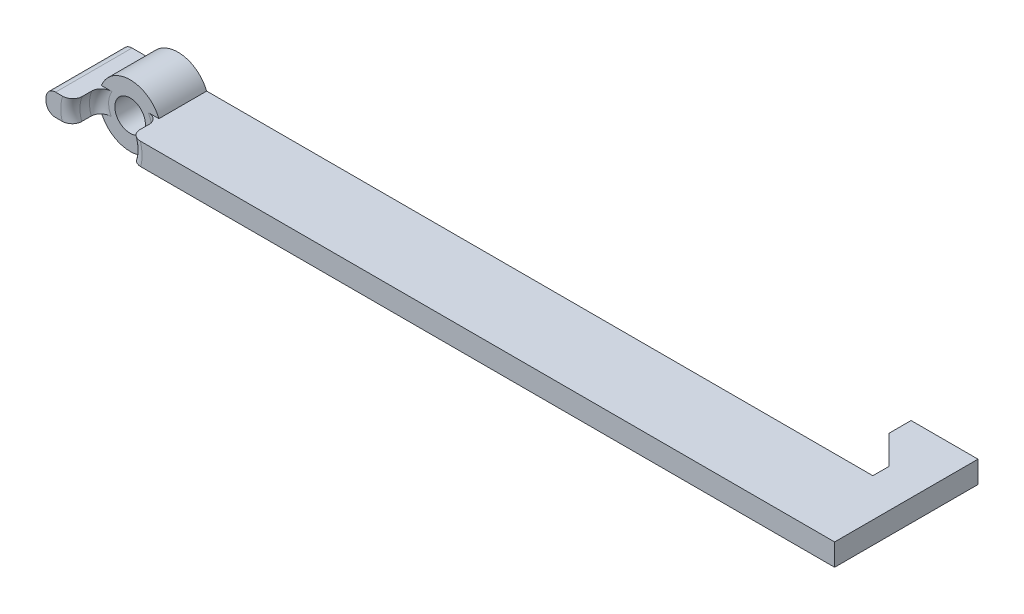
SolidWorks part; units mm, degrees
ref_plane "Front Plane" through (0, 0, 0) normal (0, 0, 1) x (1, 0, 0)
ref_plane "Top Plane" through (0, 0, 0) normal (0, 1, 0) x (1, 0, 0)
ref_plane "Right Plane" through (0, 0, 0) normal (1, 0, 0) x (0, 0, -1)
sketch "Sketch1" plane through (0, 0, 0) normal (0, 1, 0) x (1, 0, 0)
  line L0 (-78.5, 0) -> (0, 0)
  line L1 (0, 0) -> (0, 7)
  line L2 (0, 7) -> (4, 7)
  line L3 (4, 7) -> (4, -8)
  line L4 (4, -8) -> (-78.5, -8)
  line L5 (-78.5, -8) -> (-78.5, 0)
  dimension "D1" = 8
  dimension "D2" = 82.5
  dimension "D3" = 4
  dimension "D4" = 15
extrude "Boss-Extrude1" add sketch "Sketch1" along normal blind 2.3
sketch "Sketch2" plane through (0, 0, 0) normal (0, 0, -1) x (-1, 0, 0)
  line L0 (0, 2.3) -> (0, 0) construction
  circle A0 centre (72.7, 1.0768) radius 3.25
  dimension "D2" = 6.5
  dimension "D1" = 72.7
extrude "Boss-Extrude2" add sketch "Sketch2" against normal up to surface (8 mm away) up to face at (-37.25, 1.15, 8)
sketch "Sketch3" plane through (0, 0, 0) normal (0, 0, -1) x (-1, 0, 0)
  circle A0 centre (72.7, 1.0768) radius 1.6
  arc A1 (75.711, 2.3) -> (69.689, 2.3) centre (72.7, 1.0768) ccw construction
  dimension "D1" = 3.2
extrude "Cut-Extrude1" cut sketch "Sketch3" against normal up to surface (8 mm away) up to face at (-54.975, 1.1317, 8)
sketch "Sketch4" plane through (0, 0, 8) normal (0, 0, 1) x (1, 0, 0)
  circle A0 centre (-72.7, 1.0768) radius 3.25
extrude "Cut-Extrude2" cut sketch "Sketch4" against normal blind 3
fillet "Fillet1" radius 1 6 edges at (-75.9491, 1.1551, 5) (-69.4509, 1.1551, 5) (-78.5, 2.3, 4) (-75.9491, 1.1551, 8) (-69.4509, 1.1551, 8) (-78.5, 0, 4)
sketch "Sketch5" plane through (0, 0, 0) normal (-1, 0, 0) x (0, 0, 1)
  line L0 (-7, 2.3) -> (0, 2.3) construction
  line L1 (-7, 0) -> (-1.7, 0)
  line L2 (-7, 0) -> (-7, 2.3)
  line L3 (-7, 2.3) -> (-1.7, 2.3)
  line L4 (-1.7, 0) -> (-1.7, 2.3)
  line L5 (0, 2.3) -> (0, 0) construction
  dimension "D1" = 1.7
extrude "Boss-Extrude3" add sketch "Sketch5" along normal blind 3
chamfer "Chamfer1" distance 3 angle 45 1 edges at (-3, 1.15, -1.7)
